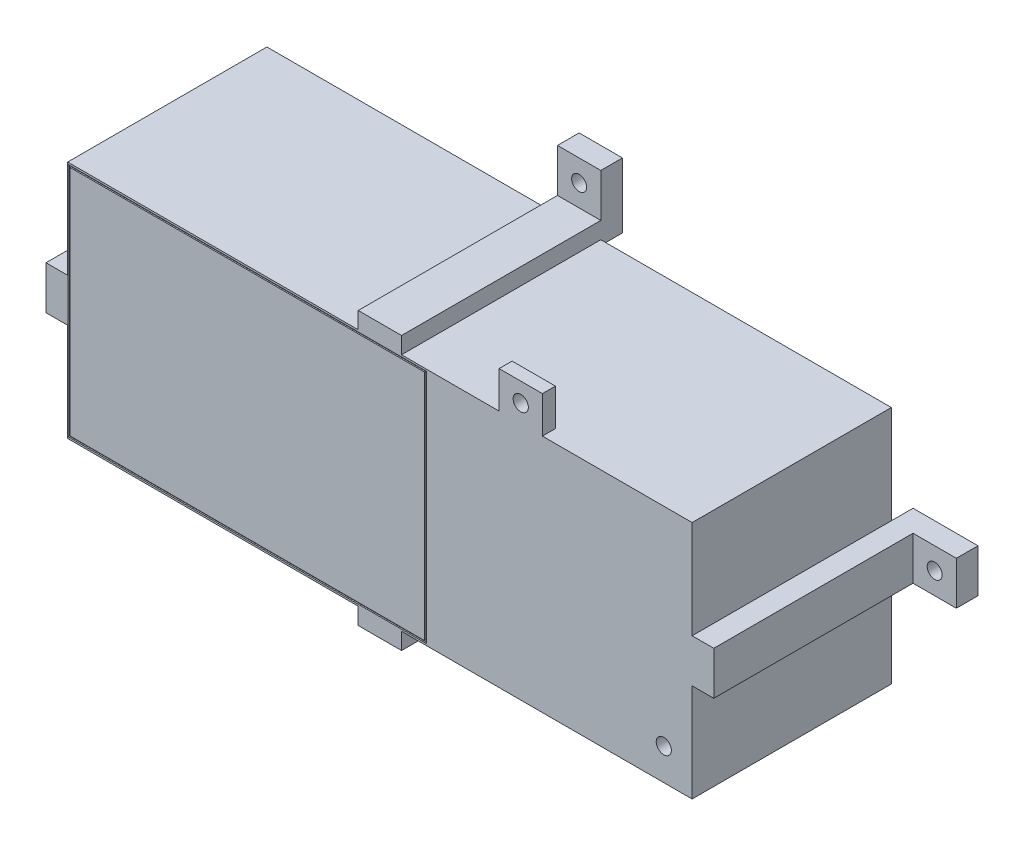
SolidWorks part; units mm, degrees
ref_plane "Front Plane" through (0, 0, 0) normal (0, 0, 1) x (1, 0, 0)
ref_plane "Top Plane" through (0, 0, 0) normal (0, 1, 0) x (1, 0, 0)
ref_plane "Right Plane" through (0, 0, 0) normal (1, 0, 0) x (0, 0, -1)
sketch "Sketch2" plane through (0, 0, 0) normal (0, 0, 1) x (1, 0, 0)
  line L0 (-68.085, -22.5) -> (68.085, 22.5) construction
  line L1 (-68.085, 22.5) -> (68.085, 22.5) construction
  line L2 (-68.085, 22.5) -> (-68.085, -22.5) construction
  line L3 (-68.085, -22.5) -> (68.085, -22.5) construction
  line L4 (68.085, 22.5) -> (68.085, -22.5) construction
  line L5 (-72.085, 26.5) -> (72.085, 26.5) construction
  line L6 (72.085, 26.5) -> (72.085, -26.5) construction
  line L7 (-72.085, -26.5) -> (72.085, -26.5) construction
  line L8 (-72.085, 26.5) -> (-72.085, -26.5) construction
  line L9 (0, 0) -> (-100, 0) construction
  line L10 (-77.085, 5) -> (-72.085, 5)
  line L11 (-77.085, 5) -> (-77.085, -5)
  line L12 (-77.085, -5) -> (-72.085, -5)
  line L13 (-72.085, 5) -> (-72.085, -5)
  line L14 (-5, 31.5) -> (5, 31.5)
  line L15 (-5, 31.5) -> (-5, 26.5)
  line L16 (-5, 26.5) -> (5, 26.5)
  line L17 (5, 31.5) -> (5, 26.5)
  line L18 (0, 0) -> (0, 108.7377) construction
  line L19 (-77.085, 5) -> (-72.085, -5) construction
  line L20 (-5, 26.5) -> (5, 31.5) construction
  line L21 (77.085, -5) -> (72.085, -5)
  line L22 (77.085, 5) -> (77.085, -5)
  line L23 (72.085, 5) -> (72.085, -5)
  line L24 (77.085, 5) -> (72.085, 5)
  line L25 (-5, -26.5) -> (5, -26.5)
  line L26 (-5, -31.5) -> (-5, -26.5)
  line L27 (-5, -31.5) -> (5, -31.5)
  line L28 (5, -31.5) -> (5, -26.5)
  point P4 (0, 0)
  point P23 (-74.585, 0)
  point P25 (0, 29)
  dimension "D1" = 45
  dimension "D2" = 136.17
  dimension "D4" = 5
  dimension "D5" = 10
  dimension "D6" = 5
  dimension "D7" = 10
  dimension "D3" = 4
extrude "Boss-Extrude1" add sketch "Sketch2" along normal blind 48
sketch "Sketch3" plane through (0, 0, 48) normal (0, 0, 1) x (1, 0, 0)
  line L0 (-82.5, 27.64) -> (82.5, -27.64) construction
  line L1 (-82.5, 27.64) -> (82.5, 27.64)
  line L2 (-82.5, 27.64) -> (-82.5, -27.64)
  line L3 (-82.5, -27.64) -> (82.5, -27.64)
  line L4 (82.5, 27.64) -> (82.5, -27.64)
  point P4 (0, 0)
  dimension "D1" = 165
  dimension "D2" = 55.28
extrude "Boss-Extrude2" add sketch "Sketch3" along normal blind 3
sketch "Sketch4" plane through (0, 0, 48) normal (0, 0, 1) x (1, 0, 0)
  line L0 (-5, 27.64) -> (5, 27.64) construction
  line L1 (5, 27.64) -> (5, 31.5) construction
  line L2 (5, 31.5) -> (-5, 31.5) construction
  line L3 (-5, 31.5) -> (-5, 27.64) construction
  line L4 (5, -31.5) -> (5, -27.64) construction
  line L5 (5, -27.64) -> (-5, -27.64) construction
  line L6 (-5, -27.64) -> (-5, -31.5) construction
  line L7 (-5, -31.5) -> (5, -31.5) construction
  line L8 (-5, 27.64) -> (5, 27.64)
  line L9 (5, 27.64) -> (5, 31.5)
  line L10 (5, 31.5) -> (-5, 31.5)
  line L11 (-5, 31.5) -> (-5, 27.64)
  line L12 (5, -31.5) -> (5, -27.64)
  line L13 (5, -27.64) -> (-5, -27.64)
  line L14 (-5, -27.64) -> (-5, -31.5)
  line L15 (-5, -31.5) -> (5, -31.5)
extrude "Boss-Extrude3" add sketch "Sketch4" along normal up to surface (3 mm away) up to face at (0, 0, 51)
sketch "Sketch5" plane through (0, 5, 0) normal (0, 1, 0) x (1, 0, 0)
  line L0 (0, 0) -> (0, -40.7206) construction
  line L1 (-77.085, 0) -> (-87.085, 0)
  line L2 (-77.085, 0) -> (-77.085, -5)
  line L3 (-77.085, -5) -> (-87.085, -5)
  line L4 (-87.085, 0) -> (-87.085, -5)
  line L5 (87.085, 0) -> (87.085, -5)
  line L6 (77.085, 0) -> (87.085, 0)
  line L7 (77.085, 0) -> (77.085, -5)
  line L8 (77.085, -5) -> (87.085, -5)
  dimension "D1" = 5
  dimension "D2" = 10
extrude "Boss-Extrude4" add sketch "Sketch5" against normal up to surface (10 mm away) up to face at (-74.585, -5, 24)
sketch "Sketch7" plane through (-5, 0, 0) normal (-1, 0, 0) x (0, 0, 1)
  line L0 (0, 0) -> (45.7182, 0) construction
  line L1 (0, 31.5) -> (5, 31.5)
  line L2 (0, 31.5) -> (0, 41.5)
  line L3 (0, 41.5) -> (5, 41.5)
  line L4 (5, 31.5) -> (5, 41.5)
  line L5 (0, -41.5) -> (5, -41.5)
  line L6 (0, -31.5) -> (0, -41.5)
  line L7 (0, -31.5) -> (5, -31.5)
  line L8 (5, -31.5) -> (5, -41.5)
  dimension "D1" = 5
  dimension "D2" = 10
extrude "Boss-Extrude5" add sketch "Sketch7" against normal up to surface (10 mm away) up to face at (5, -28.5467, 33)
sketch "Sketch8" plane through (0, 0, 5) normal (0, 0, 1) x (1, 0, 0)
  line L0 (-87.085, 5) -> (-77.085, -5) construction
  line L1 (-5, -31.5) -> (5, -41.5) construction
  line L2 (0, 0) -> (0, 49.5906) construction
  line L3 (0, 0) -> (57.6811, 0) construction
  circle A0 centre (-82.085, 0) radius 1.73
  circle A1 centre (0, -36.5) radius 1.73
  circle A2 centre (82.085, 0) radius 1.73
  circle A3 centre (0, 36.5) radius 1.73
  dimension "D1" = 3.46
  dimension "D2" = 3.46
extrude "Cut-Extrude1" cut sketch "Sketch8" against normal through all
sketch "Metro Express Layout Reference" plane through (0, 0, 51) normal (0, 0, 1) x (1, 0, 0)
  line L0 (0.32, 27.64) -> (0.32, -27.64) construction
  line L1 (14.74, 34.29) -> (68.08, 34.29) construction
  line L2 (14.74, 34.29) -> (14.74, -34.29) construction
  line L3 (14.74, -34.29) -> (68.08, -34.29) construction
  line L4 (68.08, 34.29) -> (68.08, -34.29) construction
  line L5 (82.5, -27.64) -> (82.5, 27.64) construction
  line L7 (-5, 27.64) -> (-82.5, 27.64) construction
  line L8 (-82.5, -27.64) -> (-5, -27.64) construction
  line L9 (-82.5, 27.64) -> (-82.5, -27.64) construction
  circle A0 centre (32.52, 31.75) radius 1.75 construction
  circle A1 centre (65.54, -20.32) radius 1.75 construction
  point P4 (68.08, 0)
  point P7 (82.5, 0)
  dimension "D5" = 3.5
  dimension "D7" = 3.5
  dimension "D1" = 68.58
  dimension "D2" = 53.34
  dimension "D3" = 17.78
  dimension "D4" = 2.54
  dimension "D6" = 13.97
  dimension "D8" = 2.54
  dimension "D9" = 82.82
  dimension "D10" = 14.42
sketch "Sketch10" plane through (0, 0, 51) normal (0, 0, 1) x (1, 0, 0)
  line L0 (82.5, 27.64) -> (5, 27.64) construction
  line L1 (27.52, 27.64) -> (37.52, 27.64)
  line L2 (27.52, 27.64) -> (27.52, 36.14)
  line L3 (27.52, 36.14) -> (37.52, 36.14)
  line L4 (37.52, 27.64) -> (37.52, 36.14)
  line L5 (68.08, 34.29) -> (68.08, -34.29) construction
  line L6 (68.08, -15.32) -> (69.93, -15.32)
  line L7 (68.08, -15.32) -> (68.08, -25.32)
  line L8 (68.08, -25.32) -> (69.93, -25.32)
  line L9 (69.93, -15.32) -> (69.93, -25.32)
  point P6 (32.52, 27.64)
  point P14 (68.08, -20.32)
  dimension "D1" = 8.5
  dimension "D2" = 10
  dimension "D3" = 10
  dimension "D4" = 4.39
extrude "Boss-Extrude6" add sketch "Sketch10" against normal up to surface (3 mm away) up to face at (74.585, 0, 48)
sketch "Sketch11" plane through (0, 0, 51) normal (0, 0, 1) x (1, 0, 0)
  circle A0 centre (32.52, 31.75) radius 1.75
  circle A1 centre (65.54, -20.32) radius 1.75
  circle A2 centre (32.52, 31.75) radius 1.75 construction
  circle A3 centre (65.54, -20.32) radius 1.75 construction
extrude "Cut-Extrude3" cut sketch "Sketch11" against normal through all
sketch "Sketch12" plane through (0, 0, 51) normal (0, 0, 1) x (1, 0, 0)
  line L0 (-82.5, 27.64) -> (-82.5, -27.64) construction
  line L1 (-71.785, 27.03) -> (10.535, 27.03) construction
  line L2 (-71.785, 27.03) -> (-71.785, -27.03) construction
  line L3 (-71.785, -27.03) -> (10.535, -27.03) construction
  line L4 (10.535, 27.03) -> (10.535, -27.03) construction
  line L5 (-71.985, 27.23) -> (-71.985, -27.23)
  line L6 (-12.815, 8.88) -> (12.815, 8.88) construction
  line L7 (-12.815, 8.88) -> (-12.815, -8.88) construction
  line L8 (-12.815, -8.88) -> (12.815, -8.88) construction
  line L9 (12.815, 8.88) -> (12.815, -8.88) construction
  line L10 (-71.985, -27.23) -> (10.735, -27.23)
  line L11 (10.735, 27.23) -> (10.735, -27.23)
  line L12 (-71.985, 27.23) -> (10.735, 27.23)
  line L13 (-71.585, 26.83) -> (-71.585, -26.83)
  line L14 (-71.585, -26.83) -> (10.335, -26.83)
  line L15 (10.335, 26.83) -> (10.335, -26.83)
  line L16 (-71.585, 26.83) -> (10.335, 26.83)
  point P4 (12.815, 0)
  point P5 (-71.785, 0)
  point P8 (-82.5, 0)
  point P15 (0, 8.88)
  dimension "D1" = 82.32
  dimension "D2" = 54.06
  dimension "D3" = 25.63
  dimension "D4" = 17.76
  dimension "D5" = 2.28
  dimension "D6" = 0.2
  dimension "D7" = 0.2
extrude "Cut-Extrude4" cut sketch "Sketch12" against normal blind 0.28
sketch "Sketch13" plane through (0, 0, 48) normal (0, 0, -1) x (-1, 0, 0)
  line L0 (82.5, -27.64) -> (82.5, 27.64)
  line L5 (-82.5, 27.64) -> (-82.5, -27.64)
  line L17 (-82.5, 27.64) -> (-37.52, 27.64) construction
  line L18 (-82.5, -27.64) -> (-72.085, -27.64)
  line L20 (-77.085, -5) -> (-72.085, -5)
  line L21 (-72.085, -27.64) -> (-72.085, -5)
  line L25 (-77.085, -5) -> (-77.085, 5)
  line L26 (-77.085, 5) -> (-72.085, 5)
  line L28 (-82.5, 27.64) -> (-72.085, 27.64)
  line L29 (-72.085, 5) -> (-72.085, 27.64)
  line L30 (5, 27.64) -> (82.5, 27.64) construction
  line L31 (82.5, -27.64) -> (72.085, -27.64)
  line L33 (77.085, -5) -> (72.085, -5)
  line L34 (72.085, -27.64) -> (72.085, -5)
  line L38 (77.085, -5) -> (77.085, 5)
  line L39 (77.085, 5) -> (72.085, 5)
  line L41 (82.5, 27.64) -> (72.085, 27.64)
  line L42 (72.085, 5) -> (72.085, 27.64)
extrude "Cut-Extrude5" cut sketch "Sketch13" against normal through all
sketch "Sketch14" plane through (0, 0, 48) normal (0, 0, -1) x (-1, 0, 0)
  line L0 (72.085, -5) -> (72.085, -27.64) construction
  line L1 (-72.085, 27.64) -> (-37.52, 27.64) construction
  line L2 (-27.52, 27.64) -> (-5, 27.64) construction
  line L3 (-72.085, 5) -> (-72.085, 27.64) construction
  line L4 (-5, -27.64) -> (-72.085, -27.64) construction
  line L6 (72.085, -27.64) -> (5, -27.64) construction
  line L10 (72.085, 27.64) -> (72.085, 5) construction
  line L11 (5, 27.64) -> (72.085, 27.64) construction
  line L15 (-72.085, -27.64) -> (-72.085, -5) construction
  line L157 (72.085, -5) -> (72.085, 5) construction
  line L158 (-72.085, 5) -> (-72.085, -5) construction
  line L159 (72.085, -27.64) -> (5, -27.64)
  line L160 (72.085, -5) -> (72.085, -27.64)
  line L161 (72.085, -5) -> (72.085, 5)
  line L162 (72.085, 27.64) -> (72.085, 5)
  line L163 (5, 27.64) -> (72.085, 27.64)
  line L164 (-72.085, 5) -> (-72.085, -5)
  line L165 (-72.085, -27.64) -> (-72.085, -5)
  line L166 (-5, -27.64) -> (-72.085, -27.64)
  line L167 (-72.085, 5) -> (-72.085, 27.64)
  line L168 (-27.52, 27.64) -> (-5, 27.64)
  line L169 (-72.085, 27.64) -> (-37.52, 27.64)
  line L170 (-5, -26.5) -> (-70.945, -26.5)
  line L171 (-70.945, -26.5) -> (-70.945, -5)
  line L172 (-70.945, 5) -> (-70.945, -5)
  line L173 (-70.945, 5) -> (-70.945, 26.5)
  line L174 (-70.945, 26.5) -> (-37.52, 26.5)
  line L175 (-27.52, 26.5) -> (-5, 26.5)
  line L176 (5, 26.5) -> (70.945, 26.5)
  line L177 (70.945, 26.5) -> (70.945, 5)
  line L178 (70.945, -5) -> (70.945, 5)
  line L179 (70.945, -5) -> (70.945, -26.5)
  line L180 (70.945, -26.5) -> (5, -26.5)
  line L181 (-37.52, 27.64) -> (-27.52, 27.64)
  line L182 (-37.52, 26.5) -> (-27.52, 26.5)
  line L183 (-5, -26.5) -> (-5, -27.64)
  line L184 (5, -26.5) -> (5, -27.64)
  line L185 (-5, 27.64) -> (-5, 26.5)
  line L186 (5, 27.64) -> (5, 26.5)
  dimension "D1" = 1.14
extrude "Boss-Extrude7" add sketch "Sketch14" along normal up to surface (43 mm away) up to face at (80.355, 0, 5)
